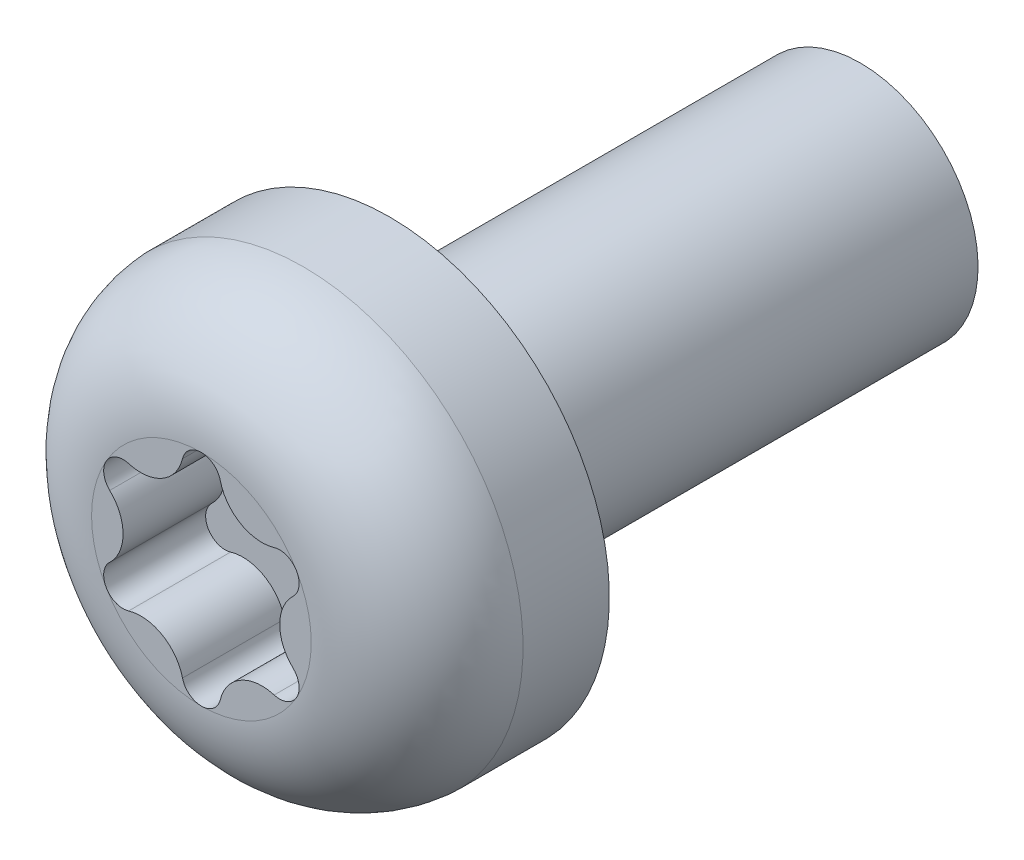
SolidWorks part; units mm, degrees
material "AISI Acier à outil type A2"
ref_plane "Face" through (0, 0, 0) normal (0, 0, 1) x (1, 0, 0)
ref_plane "Dessus" through (0, 0, 0) normal (0, 1, 0) x (1, 0, 0)
ref_plane "Droite" through (0, 0, 0) normal (1, 0, 0) x (0, 0, -1)
sketch "Esquisse1" plane through (0, 0, 0) normal (1, 0, 0) x (0, 0, -1)
  line L0 (-2.4, 0) -> (-2.4, 1.4)
  line L1 (-1.1, 2.8) -> (0, 2.8)
  line L2 (0, 2.8) -> (0, 1.5)
  line L3 (0, 1.5) -> (6, 1.5)
  line L4 (6, 1.5) -> (6, 0)
  line L5 (6, 0) -> (-2.4, 0)
  line L6 (-2.4, 0) -> (-4.3313, 0) construction
  arc A0 (-2.4, 1.4) -> (-1.1, 2.8) centre (-0.9962, 1.4) cw
  dimension "L" = 6
  dimension "K" = 2.4
  dimension "T" = 1.3
  dimension "M" = 3
  dimension "DH" = 5.6
  dimension "A" = 2.8
revolve "Révolution1" add sketch "Esquisse1" angle 360 about L6
cosmetic thread "Représentation de filetage1" parameters "D2"=2.4
sketch "Esquisse2" plane through (0, 0, 2.4) normal (0, 0, 1) x (1, 0, 0)
  line L0 (0, -1.0692) -> (0, 1.0844) construction
  line L1 (0, 0) -> (-0.1844, 0.9269) construction
  line L2 (0, 0) -> (0.1807, 0.9086) construction
  line L3 (0, 0) -> (0.8195, 0.4731) construction
  line L4 (0, 0) -> (0.7063, 0.6194) construction
  line L5 (0, 0) -> (0.3928, 0.6804) construction
  line L7 (0, 1.1524) -> (-0.998, 0.5762) construction
  line L8 (-0.998, 0.5762) -> (-0.998, -0.5762) construction
  line L9 (-0.998, -0.5762) -> (0, -1.1524) construction
  line L10 (0, -1.1524) -> (0.998, -0.5762) construction
  line L11 (0.998, -0.5762) -> (0.998, 0.5762) construction
  line L12 (0.998, 0.5762) -> (0, 1.1524) construction
  circle A0 centre (0, 0) radius 1.4 construction
  circle A1 centre (0, 0) radius 1.4 construction
  arc A2 (-0.2407, 1.2102) -> (0.2407, 1.2102) centre (0, 1.1524) cw
  circle A3 centre (0, 0) radius 0.998 construction
  arc A4 (0.2407, 1.2102) -> (0.9277, 0.8136) centre (0.7724, 1.3379) ccw
  arc A5 (0.9277, 0.8136) -> (1.1684, 0.3966) centre (0.998, 0.5762) cw
  arc A6 (1.1684, 0.3966) -> (1.1684, -0.3966) centre (1.5448, 0) ccw
  arc A7 (1.1684, -0.3966) -> (0.9277, -0.8136) centre (0.998, -0.5762) cw
  arc A8 (0.9277, -0.8136) -> (0.2407, -1.2102) centre (0.7724, -1.3379) ccw
  arc A9 (0.2407, -1.2102) -> (-0.2407, -1.2102) centre (0, -1.1524) cw
  arc A10 (-0.2407, -1.2102) -> (-0.9277, -0.8136) centre (-0.7724, -1.3379) ccw
  arc A11 (-0.9277, -0.8136) -> (-1.1684, -0.3966) centre (-0.998, -0.5762) cw
  arc A12 (-1.1684, -0.3966) -> (-1.1684, 0.3966) centre (-1.5448, 0) ccw
  arc A13 (-1.1684, 0.3966) -> (-0.9277, 0.8136) centre (-0.998, 0.5762) cw
  arc A14 (-0.9277, 0.8136) -> (-0.2407, 1.2102) centre (-0.7724, 1.3379) ccw
  point P22 (0.499, 0.8643)
  dimension "D1" = 22.5
  dimension "D2" = 60
  dimension "D3" = 11.25
  dimension "D4" = 6
extrude "Enlèv. mat.-Extru.1" cut sketch "Esquisse2" against normal blind 1.3
equation "\"D3@Esquisse2\" = \"D1@Esquisse2\"/2"
equation "\"D1@Enlèv. mat.-Extru.1\" = \"T@Esquisse1\""
